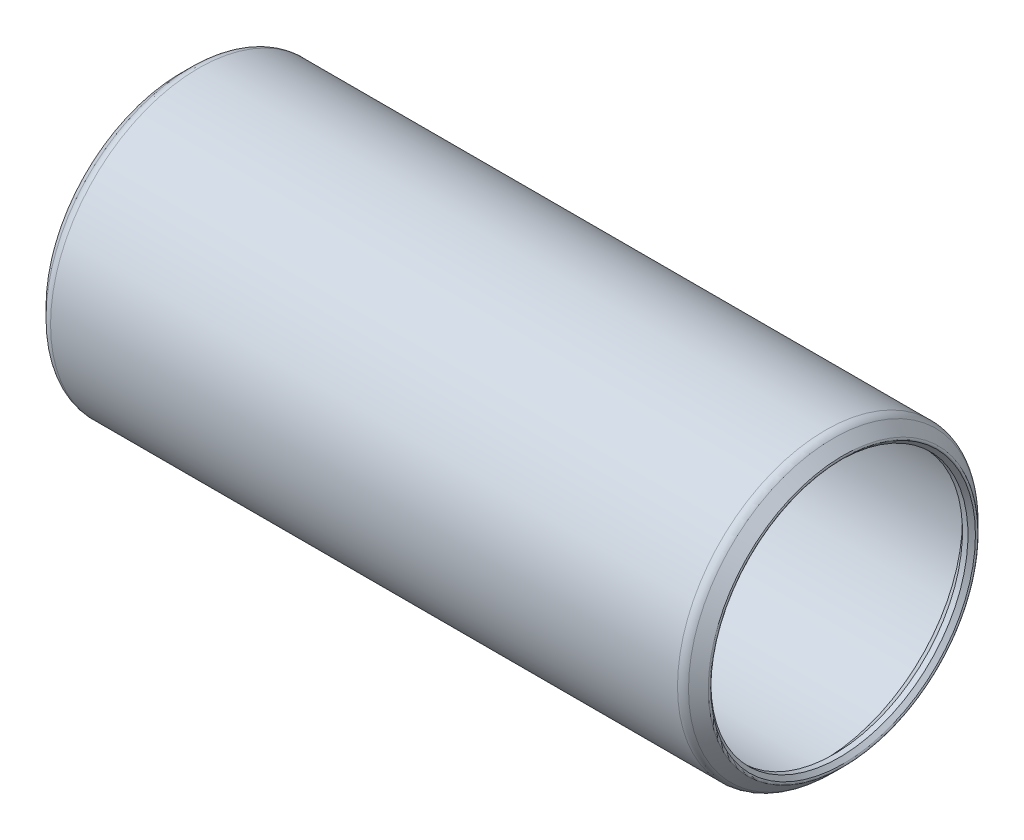
SolidWorks part; units mm, degrees
material "AISI 304"
ref_plane "Front Plane" through (0, 0, 0) normal (0, 0, 1) x (1, 0, 0)
ref_plane "Top Plane" through (0, 0, 0) normal (0, 1, 0) x (1, 0, 0)
ref_plane "Right Plane" through (0, 0, 0) normal (1, 0, 0) x (0, 0, -1)
ref_plane "Plane1" through (44.6151, 0, 0) normal (1, 0, 0) x (0, 0, -1)
sketch "Sketch1" plane through (0, 0, 0) normal (0, 0, 1) x (1, 0, 0)
  line L0 (-0.6395, 9.1676) -> (-0.381, 8.9091)
  line L1 (-0.381, 8.9091) -> (0, 8.9091)
  line L2 (0, 8.9091) -> (0.762, 9.671)
  line L3 (0.762, 9.671) -> (43.8531, 9.671)
  line L4 (43.8531, 9.671) -> (44.6151, 8.9091)
  line L5 (44.6151, 8.9091) -> (44.9961, 8.9091)
  line L6 (44.9961, 8.9091) -> (45.2546, 9.1676)
  line L7 (45.2546, 9.3472) -> (44.5697, 10.0321)
  line L8 (44.0309, 10.2553) -> (0.5842, 10.2553)
  line L9 (0.0454, 10.0321) -> (-0.6395, 9.3472)
  line L10 (44.6151, 0) -> (0, 0) construction
  arc A0 (-0.6395, 9.3472) -> (-0.6395, 9.1676) centre (-0.5497, 9.2574) ccw
  arc A1 (45.2546, 9.1676) -> (45.2546, 9.3472) centre (45.1648, 9.2574) ccw
  arc A2 (44.5697, 10.0321) -> (44.0309, 10.2553) centre (44.0309, 9.4933) ccw
  arc A3 (0.5842, 10.2553) -> (0.0454, 10.0321) centre (0.5842, 9.4933) ccw
revolve "Revolve1" add sketch "Sketch1" angle 360 about L10 reverse direction yes
ref_plane "Plane2" through (22.3075, 0, 0) normal (1, 0, 0) x (0, 0, -1)
ref_plane "cp1 XY" through (22.3075, 0, 0) normal (1, 0, 0) x (0, 0, -1)
ref_plane "cp1 XZ" through (0, 10.2553, 0) normal (0, -1, 0) x (-1, 0, 0)
ref_plane "cp1 YZ" through (0, 0, 0) normal (0, 0, -1) x (-1, 0, 0)
ref_axis "cp1 X" through (22.3075, 10.2553, 80.9) along (0, 0, -1)
ref_axis "cp1 Y" through (22.3075, -50, 0) along (0, 1, 0)
ref_axis "cp1 Z" through (80.9, 10.2553, 0) along (-1, 0, 0)
sketch3d "cp1"
  point P0 (22.3075, 10.2553, 0)
ref_plane "cp2 XY" through (22.3075, 0, 0) normal (1, 0, 0) x (0, 0, -1)
ref_plane "cp2 XZ" through (0, 0, 0) normal (0, -1, 0) x (-1, 0, 0)
ref_plane "cp2 YZ" through (0, 0, -10.2553) normal (0, 0, -1) x (-1, 0, 0)
ref_axis "cp2 X" through (22.3075, 0, 80.9) along (0, 0, -1)
ref_axis "cp2 Y" through (22.3075, -50, -10.2553) along (0, 1, 0)
ref_axis "cp2 Z" through (80.9, 0, -10.2553) along (-1, 0, 0)
sketch3d "cp2"
  point P0 (22.3075, 0, -10.2553)
ref_plane "cp3 XY" through (22.3075, 0, 0) normal (1, 0, 0) x (0, 0, -1)
ref_plane "cp3 XZ" through (0, -10.2553, 0) normal (0, -1, 0) x (-1, 0, 0)
ref_plane "cp3 YZ" through (0, 0, 0) normal (0, 0, -1) x (-1, 0, 0)
ref_axis "cp3 X" through (22.3075, -10.2553, 80.9) along (0, 0, -1)
ref_axis "cp3 Y" through (22.3075, -50, 0) along (0, 1, 0)
ref_axis "cp3 Z" through (80.9, -10.2553, 0) along (-1, 0, 0)
sketch3d "cp3"
  point P0 (22.3075, -10.2553, 0)
ref_plane "cp4 XY" through (22.3075, 0, 0) normal (1, 0, 0) x (0, 0, -1)
ref_plane "cp4 XZ" through (0, 0, 0) normal (0, -1, 0) x (-1, 0, 0)
ref_plane "cp4 YZ" through (0, 0, 10.2553) normal (0, 0, -1) x (-1, 0, 0)
ref_axis "cp4 X" through (22.3075, 0, 80.9) along (0, 0, -1)
ref_axis "cp4 Y" through (22.3075, -50, 10.2553) along (0, 1, 0)
ref_axis "cp4 Z" through (80.9, 0, 10.2553) along (-1, 0, 0)
sketch3d "cp4"
  point P0 (22.3075, 0, 10.2553)
ref_plane "tube_front XY" through (0, 0, 0) normal (1, 0, 0) x (0, 0, -1)
ref_plane "tube_front XZ" through (0, 0, 0) normal (0, -1, 0) x (-1, 0, 0)
ref_plane "tube_front YZ" through (0, 0, 0) normal (0, 0, -1) x (-1, 0, 0)
ref_axis "tube_front X" through (0, 0, 80.9) along (0, 0, -1)
ref_axis "tube_front Y" through (0, -50, 0) along (0, 1, 0)
ref_axis "tube_front Z" through (80.9, 0, 0) along (-1, 0, 0)
sketch3d "tube_front"
  point P0 (0, 0, 0)
ref_plane "tube_rear XY" through (44.6151, 0, 0) normal (1, 0, 0) x (0, 0, -1)
ref_plane "tube_rear XZ" through (0, 0, 0) normal (0, -1, 0) x (-1, 0, 0)
ref_plane "tube_rear YZ" through (0, 0, 0) normal (0, 0, -1) x (-1, 0, 0)
ref_axis "tube_rear X" through (44.6151, 0, 80.9) along (0, 0, -1)
ref_axis "tube_rear Y" through (44.6151, -50, 0) along (0, 1, 0)
ref_axis "tube_rear Z" through (80.9, 0, 0) along (-1, 0, 0)
sketch3d "tube_rear"
  point P0 (44.6151, 0, 0)
